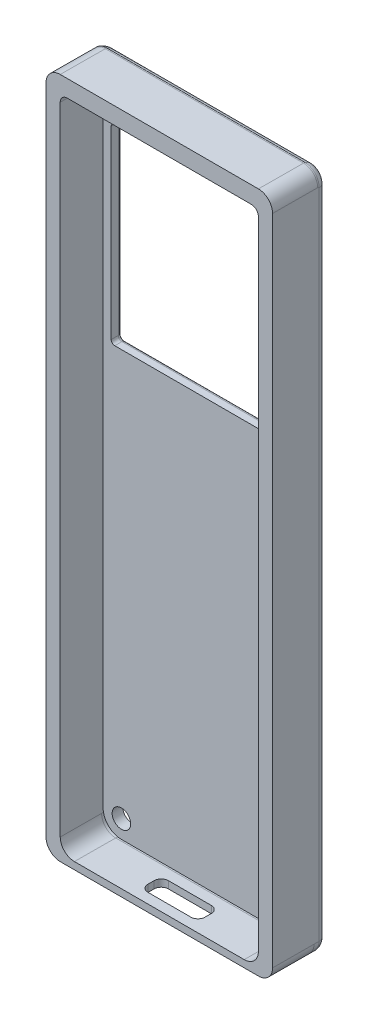
SolidWorks part; units mm, degrees
material "Plastique personnalisé"
ref_plane "Plan de face" through (0, 0, 0) normal (0, 0, 1) x (1, 0, 0)
ref_plane "Plan de dessus" through (0, 0, 0) normal (0, 1, 0) x (1, 0, 0)
ref_plane "Plan de droite" through (0, 0, 0) normal (1, 0, 0) x (0, 0, -1)
sketch "Model" plane through (0, 0, 0) normal (0, 0, 1) x (1, 0, 0)
  line L1773 (110.49, -34.8139) -> (110.49, -38.6239)
  line L1774 (83.82, -33.5439) -> (109.22, -33.5439)
  line L1775 (82.55, -38.6239) -> (82.55, -34.8139)
  line L1776 (82.55, -39.8939) -> (82.55, -123.7139)
  line L1777 (110.49, -39.8939) -> (110.49, -123.7139)
  line L1778 (82.55, -39.8939) -> (82.55, -38.6239)
  line L1779 (110.49, -39.8939) -> (110.49, -38.6239)
  line L1780 (85.09, -126.2539) -> (107.95, -126.2539)
  spline S12 degree 3 poles (110.49, -34.8139) (110.49, -34.4771) (110.3562, -34.1541) (110.118, -33.9159) knots 0 0 0 0 1 1 1 1
  spline S13 degree 3 poles (110.118, -33.9159) (109.8799, -33.6777) (109.5568, -33.5439) (109.22, -33.5439) knots 0 0 0 0 1 1 1 1
  spline S14 degree 3 poles (83.82, -33.5439) (83.4832, -33.5439) (83.1601, -33.6777) (82.922, -33.9159) knots 0 0 0 0 1 1 1 1
  spline S15 degree 3 poles (82.922, -33.9159) (82.6838, -34.1541) (82.55, -34.4771) (82.55, -34.8139) knots 0 0 0 0 1 1 1 1
  spline S16 degree 3 poles (82.55, -123.7139) (82.55, -124.3876) (82.8176, -125.0336) (83.2939, -125.51) knots 0 0 0 0 1 1 1 1
  spline S17 degree 3 poles (83.2939, -125.51) (83.7703, -125.9863) (84.4163, -126.2539) (85.09, -126.2539) knots 0 0 0 0 1 1 1 1
  spline S18 degree 3 poles (107.95, -126.2539) (108.6236, -126.2539) (109.2697, -125.9863) (109.7461, -125.51) knots 0 0 0 0 1 1 1 1
  spline S19 degree 3 poles (109.7461, -125.51) (110.2224, -125.0336) (110.49, -124.3876) (110.49, -123.7139) knots 0 0 0 0 1 1 1 1
extrude "Boss.-Extru.1" add sketch "Model" along normal blind 1.5
sketch "Esquisse2" plane through (0, 0, 1.5) normal (0, 0, 1) x (1, 0, 0)
  circle A0 centre (85.1248, -123.7139) radius 1.3048
  circle A1 centre (107.95, -123.7139) radius 1.27
extrude "Enlèv. mat.-Extru.1" cut sketch "Esquisse2" against normal blind 10
sketch "Esquisse3" plane through (0, 0, 1.5) normal (0, 0, 1) x (1, 0, 0)
  circle A2 centre (107.9434, -36.1486) radius 1.3
  circle A3 centre (85.0841, -36.0913) radius 1.3
extrude "Enlèv. mat.-Extru.2" cut sketch "Esquisse3" against normal blind 10
sketch "Esquisse4" plane through (0, 0, 0) normal (0, 0, -1) x (-1, 0, 0)
  line L0 (-82.55, -79.2639) -> (-82.55, -31.2639) construction
  line L1 (-82.55, -34.8139) -> (-82.55, -123.7139) construction
  line L2 (-96.52, -33.5439) -> (-96.52, -127.4136) construction
  line L3 (-109.22, -33.5439) -> (-83.82, -33.5439) construction
  line L4 (-82.55, -31.2639) -> (-80.55, -31.2639) construction
  line L5 (-82.55, -79.2639) -> (-80.55, -79.2639) construction
  line L6 (-80.55, -33.2639) -> (-80.55, -125.2639)
  line L7 (-96.52, -33.5439) -> (-96.52, -31.2639) construction
  line L8 (-82.55, -31.2639) -> (-110.49, -31.2639)
  line L9 (-112.49, -33.2639) -> (-112.49, -125.2639)
  line L10 (-96.52, -79.2639) -> (-112.49, -79.2639) construction
  line L11 (-82.55, -127.2639) -> (-110.49, -127.2639)
  arc A0 (-110.49, -127.2639) -> (-112.49, -125.2639) centre (-110.49, -125.2639) cw
  arc A1 (-82.55, -127.2639) -> (-80.55, -125.2639) centre (-82.55, -125.2639) ccw
  arc A2 (-82.55, -31.2639) -> (-80.55, -33.2639) centre (-82.55, -33.2639) cw
  arc A3 (-112.49, -33.2639) -> (-110.49, -31.2639) centre (-110.49, -33.2639) cw
  circle A4 centre (-107.9434, -36.1486) radius 1.3
  circle A5 centre (-85.0841, -36.0913) radius 1.3
  circle A6 centre (-107.95, -123.7139) radius 1.3
  circle A7 centre (-85.1248, -123.7139) radius 1.3048
  point P18 (-112.49, -127.2639)
  point P21 (-80.55, -127.2639)
  point P27 (-112.49, -31.2639)
  dimension "D2" = 2
  dimension "D1" = 48
extrude "Boss.-Extru.2" add sketch "Esquisse4" against normal blind 1
sketch "Esquisse5" plane through (0, 0, 0) normal (0, 0, -1) x (-1, 0, 0)
  line L1 (-109.3628, -39.3895) -> (-83.6867, -39.3895)
  line L2 (-109.3628, -39.3895) -> (-109.3628, -66.4431)
  line L3 (-109.3628, -66.4431) -> (-83.6867, -66.4431)
  line L4 (-83.6867, -39.3895) -> (-83.6867, -66.4431)
extrude "Enlèv. mat.-Extru.3" cut sketch "Esquisse5" against normal blind 10
fillet "Congé1" radius 0.5 4 edges at (83.6867, -66.4431, 0.75) (109.3628, -66.4431, 0.75) (83.6867, -39.3895, 0.75) (109.3628, -39.3895, 0.75)
fillet "Congé2" radius 0.5 8 edges at (83.8332, -39.536, 0) (83.6867, -52.9163, 0) (83.8332, -66.2966, 0) (96.5248, -66.4431, 0) (109.2164, -66.2966, 0) (109.3628, -52.9163, 0) (109.2164, -39.536, 0) (96.5248, -39.3895, 0)
sketch "Esquisse6" plane through (0, 0, 1) normal (0, 0, 1) x (1, 0, 0)
  line L0 (96.6165, -30.9202) -> (120.0647, -31.2639) construction
  line L1 (112.49, -79.2639) -> (112.49, -22.7182) construction
  line L2 (112.49, -33.2639) -> (112.49, -125.2639) construction
  line L3 (96.52, -127.2639) -> (71.7692, -127.2639) construction
  line L4 (110.49, -127.2639) -> (82.55, -127.2639) construction
  line L5 (80.55, -79.2639) -> (80.55, -134.121) construction
  line L6 (80.55, -125.2639) -> (80.55, -33.2639) construction
  line L7 (110.49, -42.8213) -> (110.49, -22.7182) construction
  line L8 (110.49, -31.1529) -> (82.55, -31.1529)
  line L9 (112.49, -33.1529) -> (112.49, -125.2639)
  line L10 (110.49, -127.2639) -> (82.55, -127.2639)
  line L11 (80.55, -33.1529) -> (80.55, -125.2639)
  line L13 (110.49, -123.7139) -> (110.49, -34.8139) construction
  line L14 (82.55, -45.62) -> (82.55, -23.2788) construction
  line L15 (109.49, -33.5439) -> (83.55, -33.5439)
  line L16 (82.55, -34.8139) -> (82.55, -123.7139) construction
  line L17 (96.52, -33.5439) -> (115.5572, -33.5439) construction
  line L18 (109.22, -33.5439) -> (83.82, -33.5439) construction
  line L19 (82.55, -101.8854) -> (82.55, -137.0547) construction
  line L20 (110.49, -34.5439) -> (110.49, -124.2539)
  line L21 (82.55, -34.8139) -> (82.55, -123.7139) construction
  line L22 (96.52, -126.2539) -> (76.0741, -126.2539) construction
  line L23 (85.09, -126.2539) -> (107.95, -126.2539) construction
  line L24 (108.49, -126.2539) -> (84.55, -126.2539)
  line L25 (82.55, -34.5439) -> (82.55, -124.2539)
  arc A0 (112.49, -125.2639) -> (110.49, -127.2639) centre (110.49, -125.2639) cw
  arc A1 (82.55, -127.2639) -> (80.55, -125.2639) centre (82.55, -125.2639) cw
  arc A2 (82.55, -31.1529) -> (80.55, -33.1529) centre (82.55, -33.1529) ccw
  arc A3 (110.49, -31.1529) -> (112.49, -33.1529) centre (110.49, -33.1529) cw
  arc A4 (84.55, -126.2539) -> (82.55, -124.2539) centre (84.55, -124.2539) cw
  arc A5 (110.49, -124.2539) -> (108.49, -126.2539) centre (108.49, -124.2539) cw
  arc A6 (83.55, -33.5439) -> (82.55, -34.5439) centre (83.55, -34.5439) ccw
  arc A7 (109.49, -33.5439) -> (110.49, -34.5439) centre (109.49, -34.5439) cw
  point P22 (80.55, -127.2639)
  point P27 (112.49, -31.1529)
  point P54 (82.55, -126.2539)
  point P61 (110.49, -33.5439)
  dimension "D1" = 2
  dimension "D2" = 2
  dimension "D3" = 1
extrude "Boss.-Extru.3" add sketch "Esquisse6" along normal up to surface (0.7168 mm away)
sketch "Esquisse8" plane through (0, 0, 0) normal (0, 0, -1) x (-1, 0, 0)
  text T0 "MORPHESP 240" font "Consolas" height in points 9
extrude "Boss.-Extru.4" add sketch "Esquisse8" along normal blind 0.1
sketch "Esquisse9" plane through (0, 0.0057, 1.0114) normal (0, 0.0056, 1) x (1, 0, 0)
  line L0 (82.55, -31.1591) -> (110.49, -31.1591)
  line L1 (112.49, -33.1591) -> (112.49, -125.2716)
  line L2 (110.49, -127.2716) -> (82.55, -127.2716)
  line L3 (80.55, -125.2716) -> (80.55, -33.1591)
  line L4 (83.55, -33.5502) -> (109.49, -33.5502)
  line L5 (110.49, -34.5502) -> (110.49, -124.2616)
  line L6 (108.49, -126.2616) -> (84.55, -126.2616)
  line L7 (84.55, -126.2616) -> (108.49, -126.2616) construction
  line L8 (82.55, -124.2616) -> (82.55, -34.5502)
  line L9 (82.55, -34.5502) -> (82.55, -34.8202) construction
  arc A0 (80.55, -33.1591) -> (82.55, -31.1591) centre (82.55, -33.1591) cw
  arc A1 (110.49, -31.1591) -> (112.49, -33.1591) centre (110.49, -33.1591) cw
  arc A2 (110.49, -127.2716) -> (112.49, -125.2716) centre (110.49, -125.2716) ccw
  arc A3 (80.55, -125.2716) -> (82.55, -127.2716) centre (82.55, -125.2716) ccw
  arc A4 (82.55, -124.2616) -> (84.55, -126.2616) centre (84.55, -124.2616) ccw
  arc A5 (82.55, -34.5502) -> (83.55, -33.5502) centre (83.55, -34.5502) cw
  arc A6 (110.49, -124.2616) -> (108.49, -126.2616) centre (108.49, -124.2616) cw
  arc A7 (109.49, -33.5502) -> (110.49, -34.5502) centre (109.49, -34.5502) cw
  ellipse E0 centre (84.55, -124.2616) end of major axis (84.55, -126.2616) minor radius 2 (82.55, -124.2616) -> (84.55, -126.2616) ccw construction
extrude "Boss.-Extru.5" add sketch "Esquisse9" along normal up to surface (6.352 mm away)
fillet "Congé3" radius 1 12 edges at (111.9042, -126.6781, 0) (96.52, -127.2639, 0) (81.1358, -126.6781, 0) (80.55, -79.2639, 0) (81.1358, -31.8497, 0) (96.52, -31.2639, 0) (111.9042, -31.8497, 0) (112.49, -79.2639, 0) (112.49, -33.2639, 0.5) (110.49, -31.2639, 0.5) (82.55, -31.2639, 0.5) (80.55, -33.2639, 0.5)
sketch "Esquisse10" plane through (0, -127.2696, 0.7168) normal (0, -1, 0.0056) x (1, 0, 0)
  line L0 (100.5308, 2.5171) -> (92.4796, 2.5171) construction
  line L2 (99.5308, 2.5171) -> (93.4796, 2.5171)
  line L3 (100.5308, 3.5171) -> (100.5308, 4.4043)
  line L4 (99.5308, 5.4043) -> (93.4796, 5.4043)
  line L5 (92.4796, 3.5171) -> (92.4796, 4.4043)
  arc A0 (100.5308, 4.4043) -> (99.5308, 5.4043) centre (99.5308, 4.4043) ccw
  arc A1 (93.4796, 5.4043) -> (92.4796, 4.4043) centre (93.4796, 4.4043) ccw
  arc A2 (92.4796, 3.5171) -> (93.4796, 2.5171) centre (93.4796, 3.5171) ccw
  arc A3 (100.5308, 3.5171) -> (99.5308, 2.5171) centre (99.5308, 3.5171) cw
  dimension "D1" = 1
extrude "Enlèv. mat.-Extru.4" cut sketch "Esquisse10" against normal blind 10
